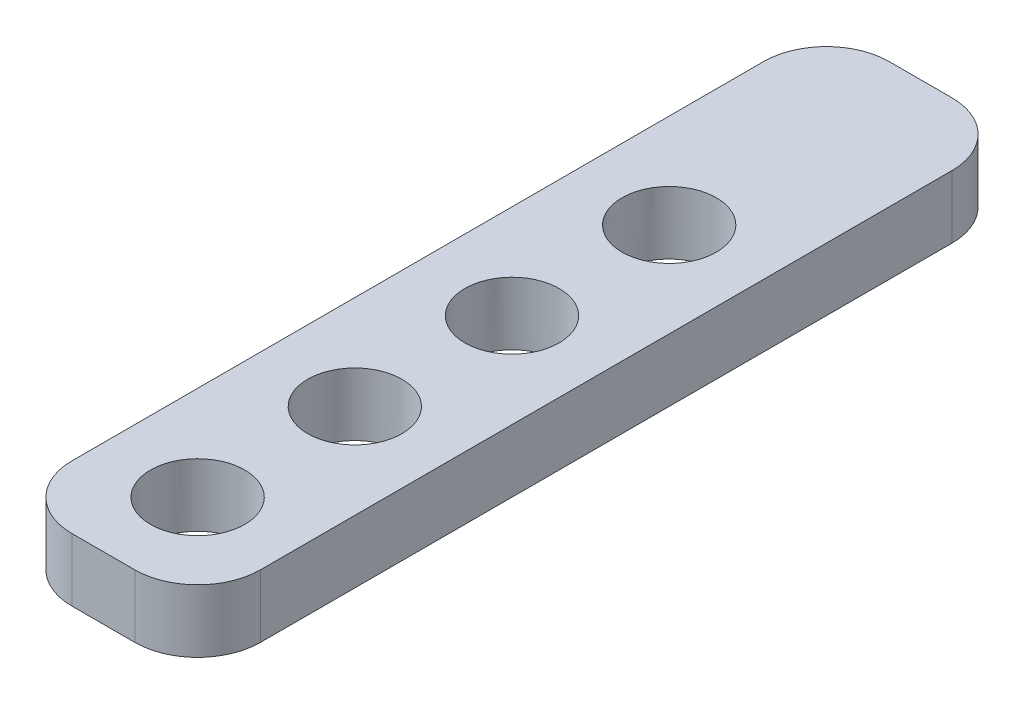
SolidWorks part; units mm, degrees
ref_plane "Front Plane" through (0, 0, 0) normal (0, 0, 1) x (1, 0, 0)
ref_plane "Top Plane" through (0, 0, 0) normal (0, 1, 0) x (1, 0, 0)
ref_plane "Right Plane" through (0, 0, 0) normal (1, 0, 0) x (0, 0, -1)
sketch "Sketch1" plane through (0, 0, 0) normal (0, 1, 0) x (1, 0, 0)
  line L1 (0, 0) -> (30, 0)
  line L2 (0, 0) -> (0, 130)
  line L3 (0, 130) -> (30, 130)
  line L4 (30, 0) -> (30, 130)
  dimension "D1" = 130
  dimension "D2" = 30
extrude "Boss-Extrude1" add sketch "Sketch1" along normal blind 10
ref_plane "Plane1" through (15, 0, 0) normal (-1, 0, 0) x (0, 0, 1)
fillet "Fillet1" radius 10 4 edges at (30, 5, -130) (30, 5, 0) (0, 5, 0) (0, 5, -130)
sketch "Sketch2" plane through (0, 10, 0) normal (0, 1, 0) x (1, 0, 0)
  line L0 (0, 15) -> (30, 15) construction
  line L1 (0, 120) -> (0, 10) construction
  line L2 (30, 10) -> (30, 120) construction
  line L3 (10, 0) -> (20, 0) construction
  circle A0 centre (15, 15) radius 7.5
  dimension "D1" = 15
  dimension "D2" = 15
extrude "Cut-Extrude1" cut sketch "Sketch2" against normal up to next
pattern_linear "LPattern1" count 4 spacing 25 along (0, 0, -1) of "Cut-Extrude1"
